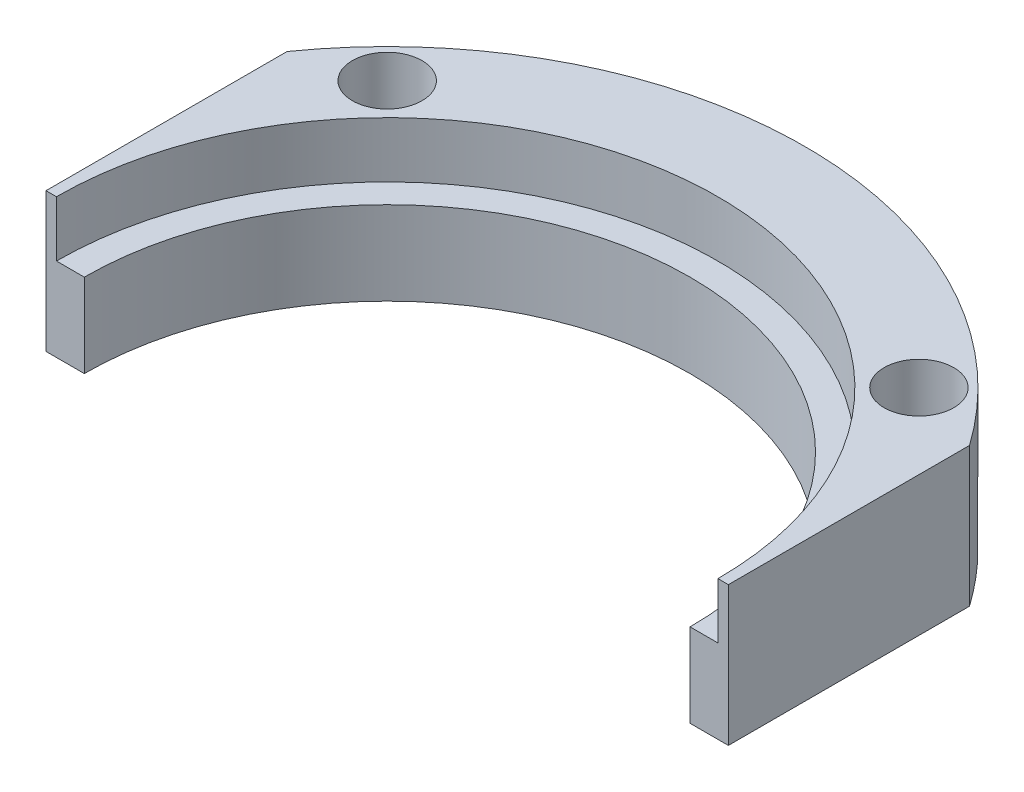
SolidWorks part; units mm, degrees
ref_plane "Front Plane" through (0, 0, 0) normal (0, 0, 1) x (1, 0, 0)
ref_plane "Top Plane" through (0, 0, 0) normal (0, 1, 0) x (1, 0, 0)
ref_plane "Right Plane" through (0, 0, 0) normal (1, 0, 0) x (0, 0, -1)
sketch "Sketch1" plane through (0, 0, 0) normal (0, 1, 0) x (1, 0, 0)
  line L0 (-49, 0) -> (49, 0)
  line L2 (-49, -34.6266) -> (-49, 34.6266)
  line L4 (49, -34.6266) -> (49, 34.6266)
  line L5 (-37.2422, -47.0427) -> (37.2422, 47.0427) construction
  line L6 (-37.2422, 47.0427) -> (37.2422, -47.0427) construction
  arc A0 (49, 34.6266) -> (-49, 34.6266) centre (0, 0) ccw
  arc A1 (-49, -34.6266) -> (49, -34.6266) centre (0, 0) ccw
  dimension "D1" = 60
  dimension "D2" = 98
extrude "Boss-Extrude1" add sketch "Sketch1" along normal blind 20 contours L4 A0 L2 L0 region at (0, 0, -26.7055)
sketch "Sketch2" plane through (0, 0, 0) normal (0, -1, 0) x (1, 0, 0)
  circle A0 centre (0, 0) radius 43.5
  dimension "D1" = 87
extrude "Cut-Extrude2" cut sketch "Sketch2" against normal through all
sketch "Sketch3" plane through (0, 20, 0) normal (0, 1, 0) x (1, 0, 0)
  circle A0 centre (0, 0) radius 47.5
  dimension "D1" = 95
extrude "Cut-Extrude3" cut sketch "Sketch3" against normal blind 8
sketch "Sketch4" plane through (0, 0, 0) normal (0, -1, 0) x (1, 0, 0)
  line L1 (-38.1838, -38.1838) -> (38.1838, -38.1838) construction
  line L2 (-38.1838, -38.1838) -> (-38.1838, 38.1838) construction
  line L3 (-38.1838, 38.1838) -> (38.1838, 38.1838) construction
  line L4 (38.1838, -38.1838) -> (38.1838, 38.1838) construction
  line L5 (-38.1838, -38.1838) -> (38.1838, 38.1838) construction
  line L6 (-38.1838, 38.1838) -> (38.1838, -38.1838) construction
  circle A0 centre (-38.1838, 38.1838) radius 6.5
  circle A1 centre (38.1838, 38.1838) radius 6.5
  circle A2 centre (38.1838, -38.1838) radius 6.5
  circle A3 centre (-38.1838, -38.1838) radius 6.5
  circle A4 centre (-38.1838, 38.1838) radius 5
  circle A5 centre (38.1838, 38.1838) radius 5
  circle A6 centre (38.1838, -38.1838) radius 5
  circle A7 centre (-38.1838, -38.1838) radius 5
  point P0 (0, 0)
  dimension "D2" = 13
  dimension "D3" = 10
  dimension "D1" = 108
extrude "Cut-Extrude4" cut sketch "Sketch4" against normal blind 10 contours A2 A6 | A6 | A7 | A3 A7 | A4 | A0 A4 | A5 | A1 A5 region at (-44.4999, 0, 38.1838) region at (31.8676, 0, 38.1838) region at (31.8676, 0, -38.1838) region at (-44.4999, 0, -38.1838) region at (-38.1838, 0, 38.1838) region at (38.1838, 0, 38.1838) region at (38.1838, 0, -38.1838) region at (-38.1838, 0, -38.1838)
extrude "Cut-Extrude6" cut sketch "Sketch4<3>" against normal through all contours A4 | A5 | A6 | A7 region at (-38.1838, 0, 38.1838) region at (38.1838, 0, 38.1838) region at (38.1838, 0, -38.1838) region at (-38.1838, 0, -38.1838)
sketch "Sketch4<3>" plane through (0, 0, 0) normal (0, -1, 0) x (1, 0, 0) same geometry as "Sketch4"
